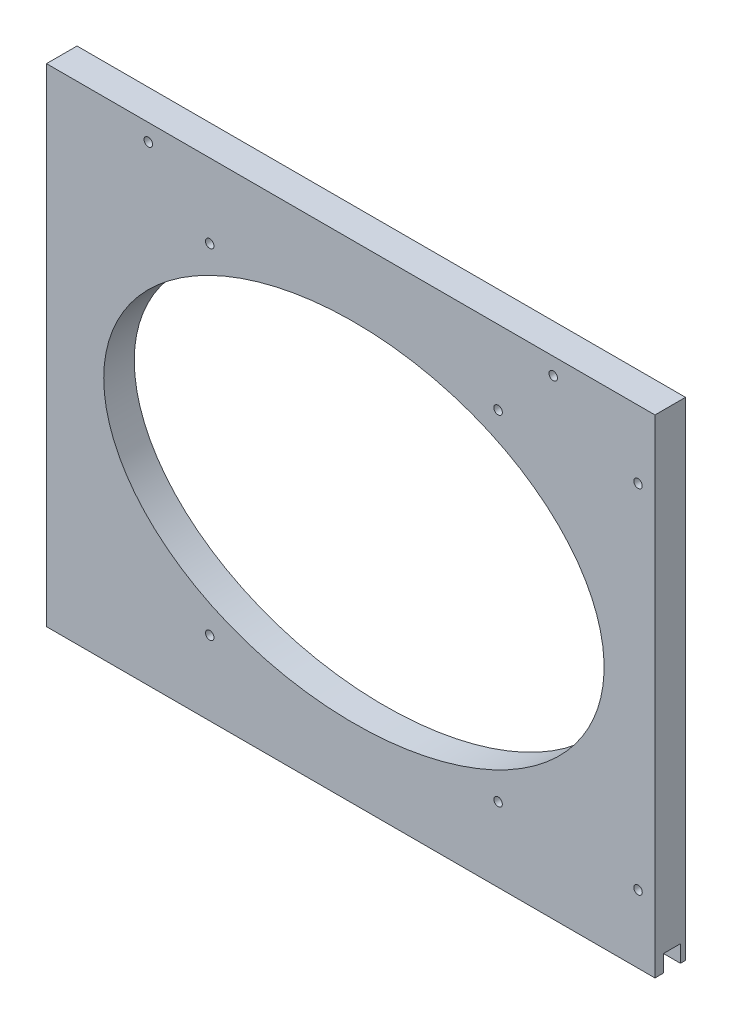
SolidWorks part; units mm, degrees
material "Pine"
ref_plane "Front Plane" through (0, 0, 0) normal (0, 0, 1) x (1, 0, 0)
ref_plane "Top Plane" through (0, 0, 0) normal (0, 1, 0) x (1, 0, 0)
ref_plane "Right Plane" through (0, 0, 0) normal (1, 0, 0) x (0, 0, -1)
sketch "Sketch1" plane through (0, 0, 0) normal (0, 0, 1) x (1, 0, 0)
  line L0 (-5300.6625, 1520.825) -> (-5451.475, 1520.825)
  line L1 (-5456.2375, 1384.3) -> (-5456.2375, 1516.0625)
  line L2 (-5557.8375, 1546.225) -> (-5194.3, 1546.225)
  line L3 (-5557.8375, 1539.875) -> (-5194.3, 1539.875)
  line L4 (-5297.4875, 1377.95) -> (-5454.65, 1377.95)
  line L5 (-5291.1375, 1384.3) -> (-5291.1375, 1516.0625)
  line L6 (-5300.6625, 1525.5875) -> (-5451.475, 1525.5875)
  line L7 (-5461, 1384.3) -> (-5461, 1516.0625)
  line L8 (-5297.4875, 1382.7125) -> (-5454.65, 1382.7125)
  line L9 (-5295.9, 1384.3) -> (-5295.9, 1516.0625)
  line L10 (-5740.4, 998.5375) -> (-5740.4, 1181.1)
  line L11 (-5740.4, 1181.1) -> (-5512.5938, 1181.1)
  line L12 (-5512.5938, 1181.1) -> (-5512.5938, 998.5375)
  line L13 (-5512.5938, 998.5375) -> (-5740.4, 998.5375)
  line L14 (-5258.5938, 1181.1) -> (-5486.4, 1181.1)
  line L15 (-5258.5938, 998.5375) -> (-5258.5938, 1181.1)
  line L16 (-5486.4, 998.5375) -> (-5258.5938, 998.5375)
  line L17 (-5486.4, 1181.1) -> (-5486.4, 998.5375)
  line L18 (-5740.4, 898.525) -> (-5011.7375, 898.525)
  line L19 (-5168.1062, 1384.3) -> (-5168.1062, 1392.2375)
  line L20 (-5176.0437, 1400.175) -> (-5245.8937, 1400.175)
  line L21 (-5253.8313, 1392.2375) -> (-5253.8313, 1384.3)
  line L22 (-5451.475, 1512.8875) -> (-5451.475, 1384.3)
  line L23 (-5303.8375, 1516.0625) -> (-5448.3, 1516.0625)
  line L24 (-5498.3062, 1384.3) -> (-5451.475, 1384.3)
  line L25 (-5253.8313, 1384.3) -> (-5300.6625, 1384.3)
  line L26 (-5584.0312, 1384.3) -> (-5740.4, 1384.3)
  line L27 (-5564.1875, 1536.7) -> (-5740.4, 1536.7)
  line L28 (-5740.4, 1357.3125) -> (-5740.4, 1206.5)
  line L29 (-5011.7375, 1357.3125) -> (-5740.4, 1357.3125)
  line L30 (-5011.7375, 1206.5) -> (-5011.7375, 1357.3125)
  line L31 (-5740.4, 1206.5) -> (-5011.7375, 1206.5)
  line L32 (-4765.675, 1549.4) -> (-4978.4, 1549.4)
  line L33 (-4765.675, 1397) -> (-4765.675, 1549.4)
  line L34 (-4978.4, 1397) -> (-4765.675, 1397)
  line L35 (-4978.4, 1549.4) -> (-4978.4, 1397)
  line L36 (-4765.675, 1371.6) -> (-4978.4, 1371.6)
  line L37 (-4765.675, 1219.2) -> (-4765.675, 1371.6)
  line L38 (-4978.4, 1219.2) -> (-4765.675, 1219.2)
  line L39 (-4978.4, 1371.6) -> (-4978.4, 1219.2)
  line L40 (-5284.7875, 803.275) -> (-5272.0875, 803.275)
  line L41 (-5187.95, 1536.7) -> (-5011.7375, 1536.7)
  line L42 (-5300.6625, 1384.3) -> (-5300.6625, 1512.8875)
  line L43 (-5740.4, 1536.7) -> (-5740.4, 1384.3)
  line L44 (-5557.8375, 1536.7) -> (-5557.8375, 1549.4)
  line L45 (-5557.8375, 1549.4) -> (-5194.3, 1549.4)
  line L46 (-5194.3, 1549.4) -> (-5194.3, 1536.7)
  line L47 (-5011.7375, 1536.7) -> (-5011.7375, 1384.3)
  line L48 (-5011.7375, 1384.3) -> (-5168.1062, 1384.3)
  line L49 (-5498.3062, 1384.3) -> (-5498.3062, 1392.2375)
  line L50 (-5506.2437, 1400.175) -> (-5576.0938, 1400.175)
  line L51 (-5584.0312, 1392.2375) -> (-5584.0312, 1384.3)
  line L52 (-5740.4, 660.4) -> (-5740.4, 898.525)
  line L53 (-5011.7375, 898.525) -> (-5011.7375, 660.4)
  line L54 (-5011.7375, 660.4) -> (-5740.4, 660.4)
  line L55 (-5291.1375, 803.275) -> (-5291.1375, 752.475)
  line L56 (-5265.7375, 752.475) -> (-5265.7375, 803.275)
  line L57 (-5284.7875, 752.475) -> (-5272.0875, 752.475)
  arc A0 (-5451.475, 1520.825) -> (-5456.2375, 1516.0625) centre (-5451.475, 1516.0625) ccw
  arc A1 (-5461, 1384.3) -> (-5454.65, 1377.95) centre (-5454.65, 1384.3) ccw
  arc A2 (-5297.4875, 1377.95) -> (-5291.1375, 1384.3) centre (-5297.4875, 1384.3) ccw
  circle A3 centre (-5037.9312, 1233.4875) radius 1.5875
  circle A4 centre (-5037.9312, 1328.7375) radius 1.5875
  circle A5 centre (-5714.2063, 1233.4875) radius 1.5875
  circle A6 centre (-5714.2063, 1328.7375) radius 1.5875
  circle A7 centre (-5018.0875, 1333.5) radius 1.5875
  circle A8 centre (-5018.0875, 1231.9) radius 1.5875
  circle A9 centre (-5734.05, 1231.9) radius 1.5875
  circle A10 centre (-5734.05, 1333.5) radius 1.5875
  circle A11 centre (-5734.05, 1511.3) radius 1.5875
  circle A12 centre (-5734.05, 1409.7) radius 1.5875
  circle A13 centre (-5018.0875, 1511.3) radius 1.5875
  circle A14 centre (-5018.0875, 1409.7) radius 1.5875
  arc A15 (-5557.8375, 1546.225) -> (-5557.8375, 1539.875) centre (-5557.8375, 1543.05) ccw
  arc A16 (-5194.3, 1539.875) -> (-5194.3, 1546.225) centre (-5194.3, 1543.05) ccw
  arc A17 (-5291.1375, 1516.0625) -> (-5300.6625, 1525.5875) centre (-5300.6625, 1516.0625) ccw
  arc A18 (-5451.475, 1525.5875) -> (-5461, 1516.0625) centre (-5451.475, 1516.0625) ccw
  arc A19 (-5456.2375, 1384.3) -> (-5454.65, 1382.7125) centre (-5454.65, 1384.3) ccw
  arc A20 (-5297.4875, 1382.7125) -> (-5295.9, 1384.3) centre (-5297.4875, 1384.3) ccw
  arc A21 (-5295.9, 1516.0625) -> (-5300.6625, 1520.825) centre (-5300.6625, 1516.0625) ccw
  circle A22 centre (-5702.3, 892.175) radius 1.5875
  circle A23 centre (-5734.05, 860.425) radius 1.5875
  circle A24 centre (-5474.8906, 892.175) radius 1.5875
  circle A25 centre (-5277.2469, 892.175) radius 1.5875
  circle A26 centre (-5049.8375, 892.175) radius 1.5875
  circle A27 centre (-5018.0875, 860.425) radius 1.5875
  circle A28 centre (-5296.6938, 1174.75) radius 1.5875
  circle A29 centre (-5448.3, 1174.75) radius 1.5875
  circle A30 centre (-5264.9437, 1155.7) radius 1.5875
  circle A31 centre (-5264.9437, 1023.9375) radius 1.5875
  circle A32 centre (-5518.9438, 1155.7) radius 1.5875
  circle A33 centre (-5518.9438, 1023.9375) radius 1.5875
  circle A34 centre (-5702.3, 1004.8875) radius 1.5875
  circle A35 centre (-5550.6937, 1004.8875) radius 1.5875
  arc A36 (-5576.0938, 1400.175) -> (-5584.0312, 1392.2375) centre (-5576.0938, 1392.2375) ccw
  arc A37 (-5168.1062, 1392.2375) -> (-5176.0437, 1400.175) centre (-5176.0437, 1392.2375) ccw
  arc A38 (-5245.8937, 1400.175) -> (-5253.8313, 1392.2375) centre (-5245.8937, 1392.2375) ccw
  arc A39 (-5448.3, 1516.0625) -> (-5451.475, 1512.8875) centre (-5448.3, 1512.8875) ccw
  arc A40 (-5284.7875, 803.275) -> (-5291.1375, 803.275) centre (-5287.9625, 803.275) ccw
  circle A41 centre (-5679.2812, 1026.3187) radius 1.5875
  circle A42 centre (-5679.2812, 1153.3187) radius 1.5875
  circle A43 centre (-5571.3313, 1153.3187) radius 1.5875
  circle A44 centre (-5571.3313, 1026.3187) radius 1.5875
  circle A45 centre (-5317.3312, 1153.3187) radius 1.5875
  circle A46 centre (-5317.3312, 1026.3187) radius 1.5875
  circle A47 centre (-5425.2812, 1026.3187) radius 1.5875
  circle A48 centre (-5425.2812, 1153.3187) radius 1.5875
  arc A49 (-5194.3, 1536.7) -> (-5187.95, 1536.7) centre (-5191.125, 1536.7) ccw
  arc A50 (-5564.1875, 1536.7) -> (-5557.8375, 1536.7) centre (-5561.0125, 1536.7) ccw
  arc A51 (-5300.6625, 1512.8875) -> (-5303.8375, 1516.0625) centre (-5303.8375, 1512.8875) ccw
  arc A52 (-5498.3062, 1392.2375) -> (-5506.2437, 1400.175) centre (-5506.2437, 1392.2375) ccw
  circle A53 centre (-5712.46, 784.225) radius 4.7625
  arc A54 (-5272.0875, 752.475) -> (-5265.7375, 752.475) centre (-5268.9125, 752.475) ccw
  arc A55 (-5291.1375, 752.475) -> (-5284.7875, 752.475) centre (-5287.9625, 752.475) ccw
  circle A56 centre (-5182.3938, 684.2125) radius 3.175
  circle A57 centre (-5239.5437, 684.2125) radius 3.175
  circle A58 centre (-5512.5938, 684.2125) radius 3.175
  circle A59 centre (-5569.7437, 684.2125) radius 3.175
  circle A60 centre (-5474.8906, 666.75) radius 1.5875
  circle A61 centre (-5277.2469, 666.75) radius 1.5875
  circle A62 centre (-5734.05, 698.5) radius 1.5875
  circle A63 centre (-5702.3, 666.75) radius 1.5875
  circle A64 centre (-5049.8375, 666.75) radius 1.5875
  circle A65 centre (-5018.0875, 698.5) radius 1.5875
  circle A66 centre (-5713.73, 835.025) radius 4.7625
  circle A67 centre (-5712.46, 819.785) radius 4.7625
  circle A68 centre (-5712.46, 802.005) radius 4.7625
  circle A69 centre (-5714.2063, 1314.45) radius 3.175
  circle A70 centre (-5037.9312, 1314.45) radius 3.175
  arc A71 (-5265.7375, 803.275) -> (-5272.0875, 803.275) centre (-5268.9125, 803.275) ccw
  ellipse E0 centre (-5371.3062, 1089.8188) end of major axis (-5277.6438, 1089.8188) minor radius 65.0875
  ellipse E1 centre (-5625.3062, 1089.8188) end of major axis (-5531.6438, 1089.8188) minor radius 65.0875
sketch "SpeakerPanel" plane through (0, 0, 0) normal (0, 0, 1) x (1, 0, 0)
  line L0 (-5258.5938, 1181.1) -> (-5258.5938, 998.5375)
  line L1 (-5258.5938, 998.5375) -> (-5486.4, 998.5375)
  line L2 (-5486.4, 998.5375) -> (-5486.4, 1181.1)
  line L3 (-5486.4, 1181.1) -> (-5258.5938, 1181.1)
  line L4 (-5372.4969, 1181.1) -> (-5372.4969, 998.5375) construction
  line L5 (-5372.4969, 1089.8188) -> (-5486.4, 1089.8188) construction
  line L6 (-5372.4969, 1089.8188) -> (-5258.5938, 1089.8188) construction
  dimension "D1" = 182.5625
  dimension "D2" = 227.8062
extrude "SpeakerPanel_Thickness" add sketch "SpeakerPanel" against normal blind 11.43
sketch "Sketch3" plane through (0, 0, 0) normal (0, 0, 1) x (1, 0, 0)
  line L0 (-5464.9688, 1089.8188) -> (-5277.6438, 1089.8188) construction
  line L1 (-5371.3062, 1154.9062) -> (-5371.3062, 1024.7313) construction
  circle A0 centre (-5448.3, 1174.75) radius 1.5875
  circle A1 centre (-5425.2812, 1153.3187) radius 1.5875
  circle A2 centre (-5296.6938, 1174.75) radius 1.5875
  circle A3 centre (-5317.3312, 1153.3187) radius 1.5875
  circle A4 centre (-5264.9437, 1155.7) radius 1.5875
  circle A5 centre (-5264.9437, 1023.9375) radius 1.5875
  circle A6 centre (-5317.3312, 1026.3187) radius 1.5875
  circle A7 centre (-5425.2812, 1026.3187) radius 1.5875
  ellipse E0 centre (-5371.3062, 1089.8188) end of major axis (-5464.9688, 1089.8188) minor radius 65.0875
extrude "SpeakerCutout" cut sketch "Sketch3" against normal up to surface (11.43 mm away) up to face at (-5372.4969, 1089.8188, -11.43)
sketch "Sketch4" plane through (-5258.5938, 0, 0) normal (1, 0, 0) x (0, 0, -1)
  line L0 (5.715, 998.5375) -> (3.175, 998.5375)
  line L1 (11.43, 998.5375) -> (0, 998.5375) construction
  line L2 (3.175, 998.5375) -> (3.175, 1004.8875)
  line L3 (3.175, 1004.8875) -> (9.525, 1004.8875)
  line L4 (9.525, 1004.8875) -> (9.525, 998.5375)
  line L5 (9.525, 998.5375) -> (5.715, 998.5375)
extrude "SpeakerSlotScreen" cut sketch "Sketch4" against normal up to surface (227.8063 mm away) up to face at (-5486.4, 1089.8188, -5.715)
